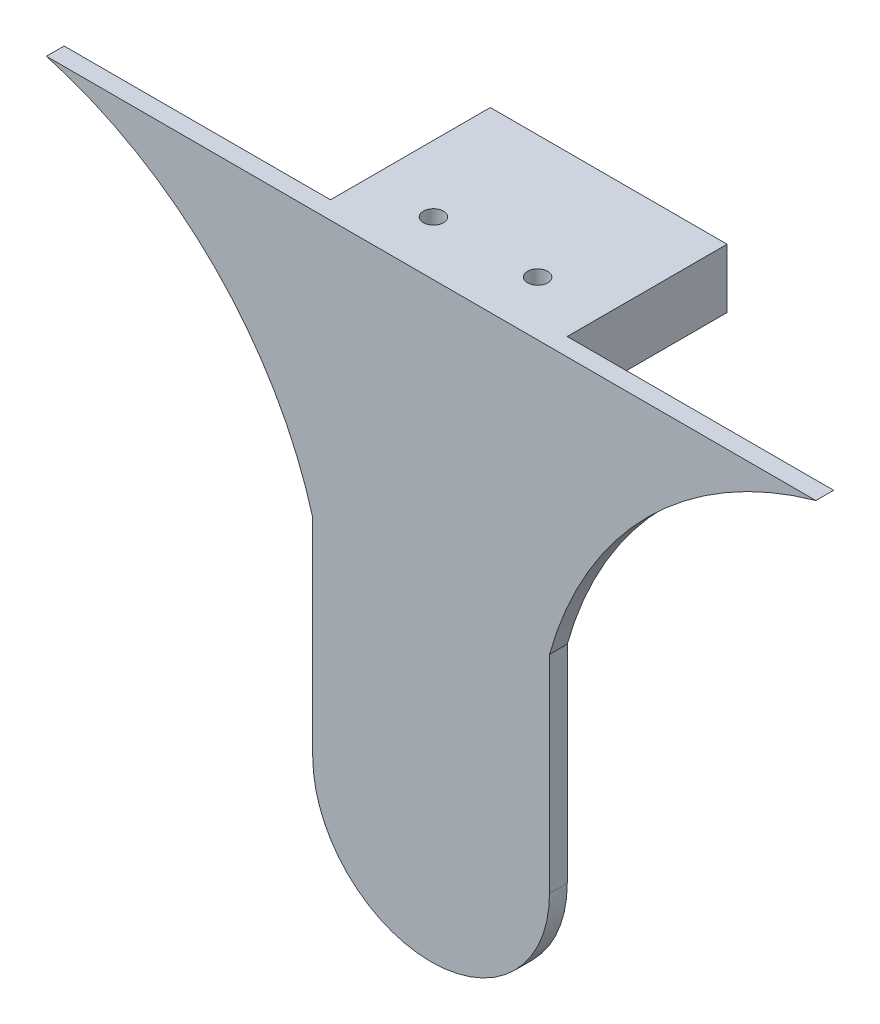
SolidWorks part; units mm, degrees
ref_plane "Front Plane" through (0, 0, 0) normal (0, 0, 1) x (1, 0, 0)
ref_plane "Top Plane" through (0, 0, 0) normal (0, 1, 0) x (1, 0, 0)
ref_plane "Right Plane" through (0, 0, 0) normal (1, 0, 0) x (0, 0, -1)
sketch "Sketch1" plane through (0, 0, 0) normal (0, 0, 1) x (1, 0, 0)
  line L1 (0, 74.4444) -> (40, 74.4444)
  line L2 (0, 74.4444) -> (0, -25.5556)
  line L3 (0, -25.5556) -> (40, -25.5556)
  line L4 (40, 74.4444) -> (40, -25.5556)
  dimension "D1" = 40
  dimension "D2" = 100
extrude "Boss-Extrude1" add sketch "Sketch1" along normal blind 3
fillet "Fillet1" radius 20 2 edges at (40, -25.5556, 1.5) (0, -25.5556, 1.5)
sketch "Sketch2" plane through (0, 0, 0) normal (0, 0, -1) x (-1, 0, 0)
  line L0 (0, 74.4444) -> (0, -5.5556) construction
  line L1 (-40, 74.4444) -> (0, 74.4444)
  line L2 (-40, 74.4444) -> (-40, 64.4444)
  line L3 (-40, 64.4444) -> (0, 64.4444)
  line L4 (0, 74.4444) -> (0, 64.4444)
  dimension "D1" = 10
extrude "Boss-Extrude2" add sketch "Sketch2" along normal blind 27
sketch "Sketch3" plane through (0, 74.4444, 0) normal (0, 1, 0) x (1, 0, 0)
  line L0 (20, -3) -> (20, 27) construction
  line L1 (40, -3) -> (0, -3) construction
  line L2 (0, 27) -> (40, 27) construction
sketch "Sketch7" plane through (0, 64.4444, 0) normal (0, -1, 0) x (1, 0, 0)
  line L0 (0, -13.5) -> (40, -13.5) construction
  line L1 (0, -27) -> (0, 0) construction
  line L2 (40, -27) -> (40, 0) construction
sketch "Sketch11" plane through (0, 64.4444, 0) normal (0, -1, 0) x (1, 0, 0)
  line L0 (20, 3) -> (20, -27) construction
  circle A0 centre (28.8, -6.1909) radius 1.5
  circle A1 centre (11.2, -6.1909) radius 1.5
  dimension "D1" = 8.8
  dimension "D2" = 8.8
hole_wizard "M3 Clearance Hole1" positions "Sketch12" profile "Sketch14" hole size "M3" standard "ANSI Metric" end condition through all
sketch "Sketch12" plane through (0, 64.4444, 0) normal (0, -1, 0) x (-1, 0, 0)
  point P0 (-28.8, 6.1909)
  point P3 (-11.2, 6.1909)
sketch "Sketch14" plane through (28.8, 64.4444, -6.1909) normal (1, 0, 0) x (0, 0, -1)
  line L0 (0, 0) -> (0, 10)
  line L1 (0, 10) -> (1.7, 10)
  line L2 (1.7, 10) -> (1.7, 0)
  line L5 (1.7, 0) -> (0, 0)
  line L11 (0, -6.35) -> (0, 107.95) construction
  dimension "Thru Hole Dia." = 3.4
  dimension "Thru Hole Depth" = 10
sketch "Sketch9" plane through (0, 64.4444, 0) normal (0, -1, 0) x (1, 0, 0)
  line L0 (20, 3) -> (20, -27) construction
  line L1 (0, -13.5) -> (40, -13.5) construction
  circle A0 centre (20, -18) radius 1.5
  circle A1 centre (20, -9) radius 1.5
  dimension "D1" = 4.5
  dimension "D2" = 4.5
sketch "Sketch15" plane through (0, 0, 3) normal (0, 0, 1) x (1, 0, 0)
  line L0 (40, 74.4444) -> (85, 74.4444)
  line L1 (20, 74.4444) -> (20, -25.5556) construction
  line L3 (0, 74.4444) -> (-45, 74.4444)
  line L4 (40, 74.4444) -> (40, -5.5556)
  line L5 (0, 74.4444) -> (0, -5.5556)
  line L6 (40, 74.4444) -> (0, 74.4444) construction
  arc A2 (85, 74.4444) -> (40, -5.5556) centre (102.5, 11.9444) ccw
  arc A3 (0, -5.5556) -> (20, -25.5556) centre (20, -5.5556) ccw construction
  arc A4 (-45, 74.4444) -> (0, -5.5556) centre (-62.5, 11.9444) cw
  line M8 (0, 74.4444) -> (0, -5.5556)
  dimension "D1" = 45
  dimension "D2" = 45
extrude "Boss-Extrude4" add sketch "Sketch15" against normal blind 3 contours A2 L0 L4 | L3 A4 M8 region at (52.1892, 62.2552, 3) region at (-12.1892, 62.2552, 3)
sketch "Sketch16" plane through (0, 0, -27) normal (0, 0, -1) x (-1, 0, 0)
  line L0 (-20, 74.4444) -> (-20, 64.4444) construction
  line L1 (0, 74.4444) -> (-40, 74.4444) construction
  line L2 (0, 64.4444) -> (-40, 64.4444) construction
